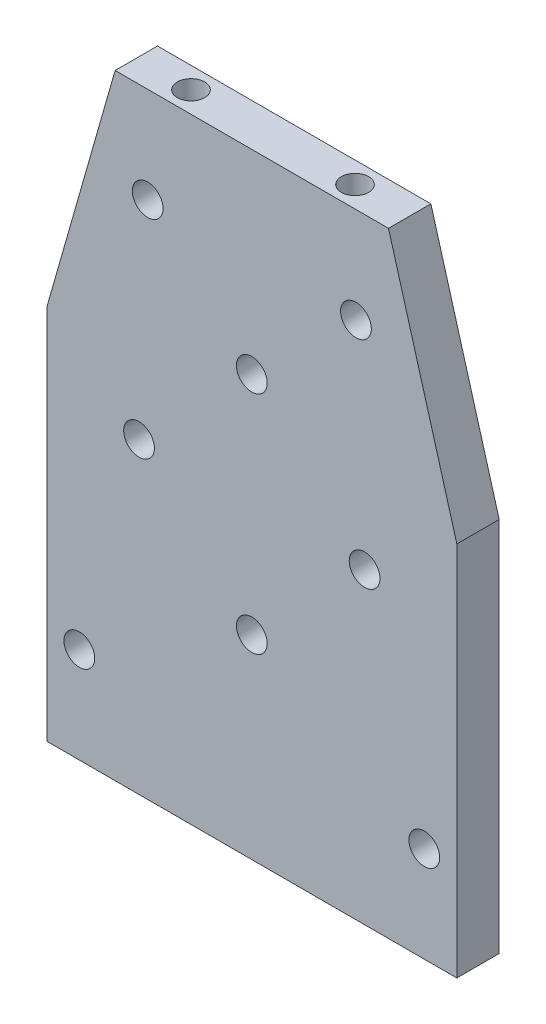
SolidWorks part; units mm, degrees
material "6061 Alloy"
ref_plane "Front Plane" through (0, 0, 0) normal (0, 0, 1) x (1, 0, 0)
ref_plane "Top Plane" through (0, 0, 0) normal (0, 1, 0) x (1, 0, 0)
ref_plane "Right Plane" through (0, 0, 0) normal (1, 0, 0) x (0, 0, -1)
sketch "Sketch1" plane through (0, 0, 0) normal (0, 0, 1) x (1, 0, 0)
  line L0 (-20, 45) -> (20, 45)
  line L5 (-30, -45) -> (30, -45)
  line L6 (0, 45) -> (0, -45) construction
  line L7 (-20, 45) -> (-30, 10)
  line L8 (-30, 10) -> (-30, -45)
  line L9 (30, 10) -> (30, -45)
  line L10 (20, 45) -> (30, 10)
  dimension "D1" = 90
  dimension "D2" = 60
  dimension "D3" = 40
  dimension "D4" = 55
extrude "1/4" add sketch "Sketch1" along normal mid plane 6.2
sketch "Sketch4" plane through (0, 45, 0) normal (0, 1, 0) x (1, 0, 0)
  line L0 (0, -3.1) -> (0, 3.1) construction
  line L1 (0, 0) -> (-12, 0) construction
  line L2 (20, -3.1) -> (-20, -3.1) construction
  line L3 (20, 3.1) -> (-20, 3.1) construction
  circle A0 centre (-12, 0) radius 2
  circle A1 centre (12, 0) radius 2
  dimension "D2" = 4
  dimension "D1" = 12
extrude "M4_DRILL" cut sketch "Sketch4" against normal blind 8
sketch "Sketch5" plane through (0, -45, 0) normal (0, -1, 0) x (-1, 0, 0)
  line L0 (0, -3.1) -> (0, 3.1) construction
  line L2 (0, 0) -> (-20, 0) construction
  line L3 (30, -3.1) -> (-30, -3.1) construction
  line L4 (30, 3.1) -> (-30, 3.1) construction
  circle A0 centre (-20, 0) radius 2
  circle A1 centre (20, 0) radius 2
  circle A2 centre (0, 0) radius 2
  dimension "D1" = 4
  dimension "D2" = 20
extrude "M4_DRILL2" cut sketch "Sketch5" against normal blind 8
sketch "Sketch6" plane through (0, 0, 3.1) normal (0, 0, 1) x (1, 0, 0)
  line L0 (-30, -45) -> (30, -45) construction
  line L1 (-30, 10) -> (-30, -45) construction
  line L2 (0, 0) -> (0, -17.9243) construction
  line L3 (20, 45) -> (-20, 45) construction
  circle A0 centre (-25.2375, -31) radius 2.25
  circle A1 centre (25.2375, -31) radius 2.25
  circle A2 centre (-15.2375, 31) radius 2.25
  circle A3 centre (15.2375, 31) radius 2.25
  dimension "D1" = 4.5
  dimension "D6" = 4.5
  dimension "D2" = 14
  dimension "D3" = 4.7625
  dimension "D4" = 14
  dimension "D5" = 4.7625
extrude "M4_through" cut sketch "Sketch6" against normal up to surface (6.2 mm away) up to face at (0, 3.3333, -3.1)
sketch "Sketch8" plane through (0, 0, -3.1) normal (0, 0, -1) x (-1, 0, 0)
  circle A0 centre (0, 0) radius 16.5 construction
  circle A1 centre (0, 16.5) radius 2.25
  circle A2 centre (16.5, 0) radius 2.25
  circle A3 centre (0, -16.5) radius 2.25
  circle A4 centre (-16.5, 0) radius 2.25
  point P14 (0, 0)
  dimension "D1" = 33
  dimension "D2" = 4.5
  dimension "D3" = 4
extrude "M4_through2" cut sketch "Sketch8" against normal blind 10
